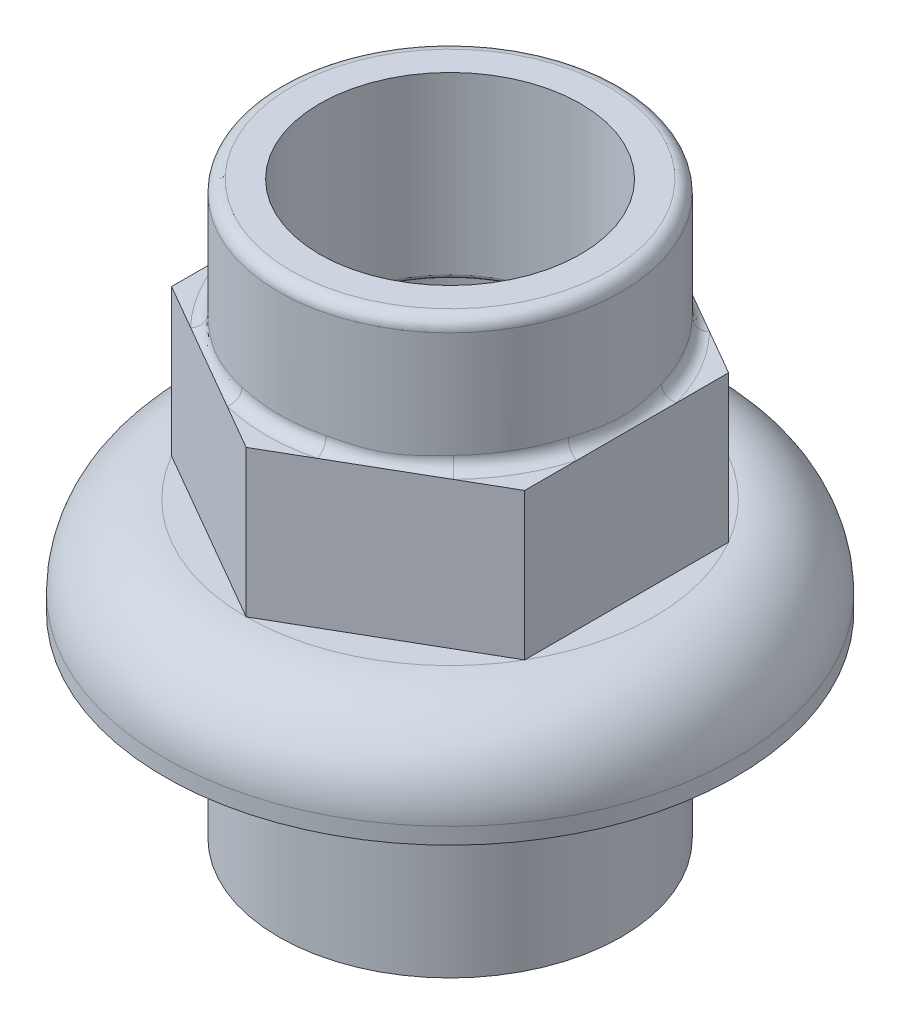
SolidWorks part; units mm, degrees
ref_plane "Front Plane" through (0, 0, 0) normal (0, 0, 1) x (1, 0, 0)
ref_plane "Top Plane" through (0, 0, 0) normal (0, 1, 0) x (1, 0, 0)
ref_plane "Right Plane" through (0, 0, 0) normal (1, 0, 0) x (0, 0, -1)
sketch "Sketch1" plane through (0, 0, 0) normal (0, 0, 1) x (1, 0, 0)
  line L0 (0, 0) -> (0, 21.647) construction
  line L1 (-29, -12.7254) -> (-29, -9.7254)
  line L2 (-16, 33.2746) -> (-16, 11.2746)
  line L3 (-17, 8.2746) -> (-9, 8.2746)
  line L4 (-9, 8.2746) -> (-9, 1.2746)
  line L5 (-9, 1.2746) -> (-16.5, 1.2746)
  line L6 (-16.5, 1.2746) -> (-16.5, -6.7254)
  line L7 (-16.5, -6.7254) -> (-15, -6.7254)
  line L8 (-15, -6.7254) -> (-15, -36.7254)
  line L9 (-15, -36.7254) -> (-21, -36.7254)
  line L10 (-21, -36.7254) -> (-21, -15.7254)
  line L11 (-21, -15.7254) -> (-20.5, -15.7089)
  line L12 (-16, 11.2746) -> (-17, 11.2746)
  line L13 (-29, -12.7254) -> (-35, -12.7254)
  line L14 (-35, -12.7254) -> (-35, -0.7254)
  line L15 (-35, -0.7254) -> (-25, -0.7254)
  line L16 (-25, -0.7254) -> (-25, 17.2746)
  line L17 (-25, 17.2746) -> (-21, 17.2746)
  line L18 (-21, 17.2746) -> (-21, 33.2746)
  line L19 (-21, 33.2746) -> (-16, 33.2746)
  line L20 (-29, -9.7254) -> (-20.5, -9.7254)
  line L21 (-20.5, -9.7254) -> (-20.5, -15.7089)
  line L22 (-17, 11.2746) -> (-17, 8.2746)
  dimension "D1" = 18
  dimension "D2" = 32
  dimension "D3" = 33
  dimension "D4" = 30
  dimension "D5" = 42
  dimension "D6" = 58
  dimension "D7" = 70
  dimension "D8" = 50
  dimension "D9" = 42
  dimension "D10" = 21
  dimension "D11" = 24
  dimension "D12" = 36
  dimension "D13" = 18
  dimension "D14" = 70
  dimension "D15" = 30
  dimension "D16" = 38
  dimension "D17" = 22
  dimension "D18" = 25
  dimension "D19" = 1
  dimension "D20" = 27
revolve "Revolve1" add sketch "Sketch1" angle 360 about L0
fillet "Fillet1" radius 10 1 edges at (0, -0.7254, -35)
sketch "Sketch2" plane through (0, 17.2746, 0) normal (0, 1, 0) x (-1, 0, 0)
  line L1 (0, -25) -> (21.6506, -12.5)
  line L2 (21.6506, -12.5) -> (21.6506, 12.5)
  line L3 (21.6506, 12.5) -> (0, 25)
  line L4 (0, 25) -> (-21.6506, 12.5)
  line L5 (-21.6506, 12.5) -> (-21.6506, -12.5)
  line L6 (-21.6506, -12.5) -> (0, -25)
  circle A0 centre (0, 0) radius 21.6506 construction
  circle A1 centre (0, 0) radius 40.1866
  dimension "D1" = 50
extrude "Cut-Extrude1" cut sketch "Sketch2" against normal blind 18
fillet "Fillet2" radius 0.5 2 edges at (0, 8.2746, -17) (0, 11.2746, -16)
fillet "Fillet3" radius 1.5 2 edges at (0, 33.2746, -21) (0, 17.2746, -21)
fillet "Fillet4" radius 1 3 edges at (0, -9.7254, -20.5) (0, -9.7254, -29) (0, -12.7254, -29)
